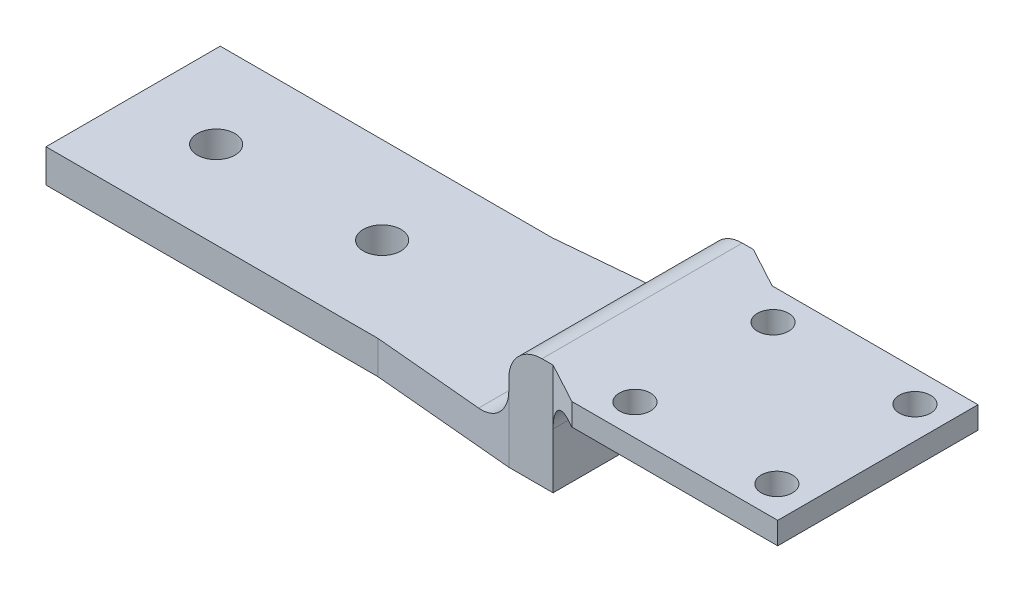
SolidWorks part; units mm, degrees
material "ABS"
ref_plane "Front Plane" through (0, 0, 0) normal (0, 0, 1) x (1, 0, 0)
ref_plane "Top Plane" through (0, 0, 0) normal (0, 1, 0) x (1, 0, 0)
ref_plane "Right Plane" through (0, 0, 0) normal (1, 0, 0) x (0, 0, -1)
sketch "Profile" plane through (0, 0, 0) normal (1, 0, 0) x (0, 0, -1)
  line L0 (-20, 4.445) -> (-20, 9.845) construction
  line L1 (-20, 4.445) -> (20, 4.445) construction
  line L2 (-20, 4.445) -> (-20, 24.445) construction
  line L3 (-20, 24.445) -> (20, 24.445) construction
  line L4 (20, 4.445) -> (20, 24.445) construction
  line L5 (-20, 4.445) -> (20, 24.445) construction
  line L6 (-20, 24.445) -> (20, 4.445) construction
  line L7 (-20, 9.845) -> (-18.5, 11.345) construction
  line L8 (-14.5, 10.6526) -> (-14.5, 18.2374) construction
  line L9 (0, 14.445) -> (-20, 14.445) construction
  line L10 (0, 14.445) -> (0, 4.445) construction
  line L11 (-20, 4.445) -> (-14.6, 4.445) construction
  line L12 (-14.6, 4.445) -> (-13.1, 5.945) construction
  line L13 (-13.1, 5.945) -> (-15.5, 5.945) construction
  line L14 (-15.5, 5.945) -> (-15.5, 7.445) construction
  line L15 (-15.5, 7.445) -> (-13.1, 9.945) construction
  line L16 (-13.1, 9.945) -> (-6.9, 9.945) construction
  line L17 (-6.9, 9.945) -> (-4.5, 7.445) construction
  line L18 (-4.5, 7.445) -> (-4.5, 5.945) construction
  line L19 (-4.5, 5.945) -> (-6.9, 5.945) construction
  line L20 (-6.9, 5.945) -> (-5.4, 4.445) construction
  line L21 (-5.4, 4.445) -> (5.4, 4.445) construction
  line L22 (-3, 5.945) -> (-3, 8.0485) construction
  line L23 (-3, 5.945) -> (3, 5.945) construction
  line L24 (0, 5.945) -> (0, 4.445) construction
  line L25 (-14.5, 14.445) -> (-12.1, 14.445) construction
  line L26 (-7.9, 14.445) -> (-5.5, 14.445) construction
  line L27 (-5.5, 18.2374) -> (-5.5, 10.6526) construction
  line L28 (-5.5, 10.6526) -> (-3, 8.0485) construction
  line L29 (-13.1, 9.945) -> (-13.1, 5.945) construction
  line L30 (-13.1, 5.945) -> (-6.9, 5.945) construction
  line L31 (-6.9, 9.945) -> (-6.9, 5.945) construction
  line L32 (-18.5, 11.345) -> (-18.5, 8.0485) construction
  line L33 (-18.5, 8.0485) -> (-17, 8.0485) construction
  line L34 (-15.5, 7.445) -> (-4.5, 7.445) construction
  line L35 (-17, 8.0485) -> (-14.5, 10.6526) construction
  line L36 (-13.1, 9.945) -> (-6.9, 9.945) construction
  line L37 (-10, 9.945) -> (-10, 14.445) construction
  line L38 (-18.5, 8.0485) -> (-20, 8.0485) construction
  line L39 (-15.5, 5.945) -> (-15.5, 4.445) construction
  line L40 (-4.5, 5.945) -> (-4.5, 4.445) construction
  line L41 (-17, 8.0485) -> (-3, 8.0485) construction
  line L42 (-18.5, 11.345) -> (-20, 11.345) construction
  line L43 (-18.5, 20.8415) -> (-17, 20.8415) construction
  line L44 (-18.5, 17.545) -> (-18.5, 20.8415) construction
  line L45 (-20, 19.045) -> (-18.5, 17.545) construction
  line L46 (-20, 24.445) -> (-20, 19.045) construction
  line L47 (-20, 24.445) -> (-14.6, 24.445) construction
  line L48 (-14.6, 24.445) -> (-13.1, 22.945) construction
  line L49 (-13.1, 22.945) -> (-15.5, 22.945) construction
  line L50 (-15.5, 22.945) -> (-15.5, 21.445) construction
  line L51 (-15.5, 21.445) -> (-13.1, 18.945) construction
  line L52 (-13.1, 18.945) -> (-6.9, 18.945) construction
  line L53 (-6.9, 18.945) -> (-4.5, 21.445) construction
  line L54 (-4.5, 21.445) -> (-4.5, 22.945) construction
  line L55 (-4.5, 22.945) -> (-6.9, 22.945) construction
  line L56 (-6.9, 22.945) -> (-5.4, 24.445) construction
  line L57 (-5.4, 24.445) -> (5.4, 24.445) construction
  line L58 (0, 22.945) -> (0, 24.445)
  line L59 (-3, 22.945) -> (3, 22.945) construction
  line L60 (-3, 22.945) -> (-3, 20.8415) construction
  line L61 (-5.5, 18.2374) -> (-3, 20.8415) construction
  line L62 (-17, 20.8415) -> (-14.5, 18.2374) construction
  line L63 (18.5, 17.545) -> (18.5, 20.8415) construction
  line L64 (20, 19.045) -> (18.5, 17.545) construction
  line L65 (20, 24.445) -> (20, 19.045) construction
  line L66 (20, 24.445) -> (14.6, 24.445) construction
  line L67 (14.6, 24.445) -> (13.1, 22.945) construction
  line L68 (13.1, 22.945) -> (15.5, 22.945) construction
  line L69 (15.5, 22.945) -> (15.5, 21.445) construction
  line L70 (15.5, 21.445) -> (13.1, 18.945) construction
  line L71 (13.1, 18.945) -> (6.9, 18.945) construction
  line L72 (6.9, 18.945) -> (4.5, 21.445) construction
  line L73 (4.5, 21.445) -> (4.5, 22.945) construction
  line L74 (4.5, 22.945) -> (6.9, 22.945) construction
  line L75 (6.9, 22.945) -> (5.4, 24.445) construction
  line L76 (3, 22.945) -> (3, 20.8415) construction
  line L77 (5.5, 18.2374) -> (3, 20.8415) construction
  line L78 (5.5, 18.2374) -> (5.5, 10.6526) construction
  line L79 (5.5, 10.6526) -> (3, 8.0485) construction
  line L80 (3, 5.945) -> (3, 8.0485) construction
  line L81 (6.9, 5.945) -> (5.4, 4.445) construction
  line L82 (4.5, 5.945) -> (6.9, 5.945) construction
  line L83 (4.5, 7.445) -> (4.5, 5.945) construction
  line L84 (6.9, 9.945) -> (4.5, 7.445) construction
  line L85 (13.1, 9.945) -> (6.9, 9.945) construction
  line L86 (15.5, 7.445) -> (13.1, 9.945) construction
  line L87 (15.5, 5.945) -> (15.5, 7.445) construction
  line L88 (13.1, 5.945) -> (15.5, 5.945) construction
  line L89 (14.6, 4.445) -> (13.1, 5.945) construction
  line L90 (20, 4.445) -> (14.6, 4.445) construction
  line L91 (20, 4.445) -> (20, 9.845) construction
  line L92 (20, 9.845) -> (18.5, 11.345) construction
  line L93 (18.5, 11.345) -> (18.5, 8.0485) construction
  line L94 (18.5, 8.0485) -> (17, 8.0485) construction
  line L95 (17, 8.0485) -> (14.5, 10.6526) construction
  line L96 (14.5, 10.6526) -> (14.5, 18.2374) construction
  line L97 (17, 20.8415) -> (14.5, 18.2374) construction
  line L98 (18.5, 20.8415) -> (17, 20.8415) construction
  line L101 (20, 1.905) -> (20, -1.905)
  line L104 (20, 1.905) -> (-20, -1.905) construction
  line L105 (20, -1.905) -> (-20, 1.905) construction
  line L115 (20, 1.905) -> (-20, 1.905) construction
  line L116 (-20, 1.905) -> (-20, -1.905) construction
  line L117 (-20, -1.905) -> (20, -1.905) construction
  line L118 (20, -1.905) -> (15.08, -1.905)
  line L121 (10, -1.905) -> (20, -1.905) construction
  line L129 (4.92, -1.905) -> (2.7203, -5.715) construction
  line L130 (2.7203, -5.715) -> (0, -5.715) construction
  line L132 (20, -5.715) -> (20, -1.905) construction
  line L137 (20, -5.715) -> (17.2797, -5.715) construction
  line L138 (17.2797, -5.715) -> (15.08, -1.905) construction
  line L139 (0, 0) -> (0, -5.715) construction
  line L142 (15.08, -1.905) -> (10, -1.905)
  line L144 (10, -1.905) -> (4.92, -1.905)
  line L150 (4.92, -1.905) -> (0, -1.905)
  line L164 (0, 1.905) -> (20, 1.905)
  line L165 (0, 1.905) -> (0, -1.905)
  line L166 (0, -5.715) -> (0, -1.905) construction
  circle A0 centre (-10, 14.445) radius 2.1 construction
  circle A1 centre (10, 14.445) radius 2.1 construction
  point P0 (0, 14.445)
  point P105 (0, 0)
  point P106 (10, -1.905)
  dimension "D3" = 2.1
  dimension "D1" = 40
  dimension "D2" = 20
  dimension "D4" = 45
  dimension "D5" = 45
  dimension "D6" = 1.5
  dimension "D7" = 6.2
  dimension "D8" = 11
  dimension "D9" = 45
  dimension "D10" = 10
  dimension "D11" = 1.5
  dimension "D12" = 3.1
  dimension "D13" = 5.5
  dimension "D14" = 5.5
  dimension "D15" = 1.5
  dimension "D16" = 1.5
  dimension "D17" = 3.81
  dimension "D18" = 3.81
  dimension "D19" = 2.7203
  dimension "D20" = 2.54
  dimension "D21" = 60
  dimension "D22" = 5.08
  dimension "D23" = 5.08
  dimension "D25" = 60
extrude "Body" add sketch "Profile" along normal blind 38.1 contours L142 L144 L150 L165 L164 L101 L118
sketch "Sketch10" plane through (0, -1.905, 0) normal (0, -1, 0) x (-1, 0, 0)
  line L0 (0, 10) -> (-9.525, 10) construction
  line L1 (0, 20) -> (0, 0) construction
  line L2 (-9.525, 10) -> (-28.575, 10) construction
  line L3 (-28.575, 10) -> (-38.1, 10) construction
  line L4 (-38.1, 20) -> (-38.1, 0) construction
  dimension "D1" = 9.525
  dimension "D2" = 9.525
hole_wizard "13/64 (0.20313) Diameter Hole1" positions "Sketch4" profile "Sketch5" hole size "13/64" standard "ANSI Inch"
sketch "Sketch4" plane through (0, -1.905, 0) normal (0, -1, 0) x (-1, 0, 0)
  point P60 (-28.575, 10)
  point P63 (-9.525, 10)
sketch "Sketch5" plane through (28.575, -1.905, -10) normal (1, 0, 0) x (0, 0, -1)
  line L0 (0, 0) -> (0, 5.1061)
  line L1 (0, 5.1061) -> (2.5798, 3.556)
  line L2 (2.5798, 3.556) -> (2.5798, 0)
  line L5 (2.5798, 0) -> (0, 0)
  line L10 (0, 5.1061) -> (-2.5798, 3.556) construction
  line L11 (0, -6.35) -> (0, 107.95) construction
  dimension "Hole Dia." = 5.1595
  dimension "Hole Depth" = 3.556
  dimension "Drill Angle" = 118
chamfer "Chamfer1" distance 0.635 angle 30 2 edges at (9.525, -1.905, -12.5798) (28.575, -1.905, -12.5798) first distance on face at (28.575, -1.905, -12.5798)
sketch "Sketch8" plane through (0, -1.905, 0) normal (0, 1, 0) x (1, 0, 0)
  line L0 (38.1, 10) -> (76.2, 10) construction
  line L1 (38.1, 0) -> (38.1, 20) construction
  dimension "D1" = 38.1
sketch "Sketch9" plane through (0, -1.905, 0) normal (0, 1, 0) x (1, 0, 0)
  line L6 (38.1, 10) -> (59.69, 10) construction
  line L8 (38.1, 20) -> (38.1, 0) construction
  line L9 (38.1, 20) -> (38.1, 0)
  line L14 (59.69, 21.4935) -> (59.69, -1.4935)
  line L15 (59.69, -1.4935) -> (54.61, -1.4935)
  line L16 (54.61, -1.4935) -> (54.61, 21.4935) construction
  line L17 (54.61, 21.4935) -> (59.69, 21.4935)
  line L18 (38.1, 20) -> (54.61, 21.4935)
  line L19 (38.1, 0) -> (54.61, -1.4935)
  line M21 (38.1, 20) -> (38.1, 0)
  dimension "D1" = 21.59
  dimension "D2" = 22.987
  dimension "D3" = 5.08
extrude "Reacher" add sketch "Sketch9" along normal blind 3.81 contours L14 M21 | L14 region at (49.1717, -1.905, -10)
sketch "Sketch13" plane through (0, 1.905, 0) normal (0, 1, 0) x (1, 0, 0)
  line L1 (59.69, 21.4935) -> (54.61, 21.4935)
  line L2 (59.69, 21.4935) -> (59.69, -1.4935)
  line L3 (59.69, -1.4935) -> (54.61, -1.4935)
  line L4 (54.61, 21.4935) -> (54.61, -1.4935)
  line L5 (59.69, 21.4935) -> (54.61, -1.4935) construction
  line L6 (59.69, -1.4935) -> (54.61, 21.4935) construction
  point P4 (57.15, 10)
extrude "Boss-Extrude4" add sketch "Sketch13" along normal blind 8.89
sketch "Sketch11" plane through (0, 10.795, 0) normal (0, 1, 0) x (1, 0, 0)
  line L0 (59.69, -1.4935) -> (59.69, 21.4935) construction
  line L1 (64.389, -4.0335) -> (88.011, -4.0335)
  line L2 (64.389, -4.0335) -> (64.389, 18.9535) construction
  line L3 (64.389, 18.9535) -> (88.011, 18.9535)
  line L4 (88.011, -4.0335) -> (88.011, 18.9535)
  line L5 (64.389, -4.0335) -> (88.011, 18.9535) construction
  line L6 (64.389, 18.9535) -> (88.011, -4.0335) construction
  line L7 (59.69, -1.4935) -> (64.389, -4.0335)
  line L8 (64.389, 18.9535) -> (59.69, 21.4935)
  line L9 (68.0563, 15.3848) -> (84.3437, 15.3848) construction
  line L10 (84.3437, 15.3848) -> (84.3437, -0.4648) construction
  line L11 (84.3437, -0.4648) -> (68.0563, -0.4648) construction
  line L12 (68.0563, -0.4648) -> (68.0563, 15.3848) construction
  line L13 (59.69, 21.4935) -> (59.69, -1.4935)
  circle A0 centre (68.0563, 15.3848) radius 1.7907
  circle A1 centre (84.3437, 15.3848) radius 1.7907
  circle A2 centre (84.3437, -0.4648) radius 1.7907
  circle A3 centre (68.0563, -0.4648) radius 1.7907
  point P4 (76.2, 7.46)
  point P6 (59.69, 10)
  point P7 (64.389, 24.0335)
  point P19 (68.0563, 17.1755)
  point P20 (59.69, 21.0288)
  point P27 (0, 0)
  dimension "D4" = 3.5814
  dimension "D1" = 23.622
  dimension "D2" = 22.987
  dimension "D3" = 1.778
  dimension "D5" = 4.699
  dimension "D6" = 2.54
extrude "Boss-Extrude3" add sketch "Sketch11" against normal blind 2.54
fillet "Fillet1" radius 3.81 3 edges at (54.61, 1.905, -10) (59.69, 8.255, -10) (54.61, 10.795, -10)
